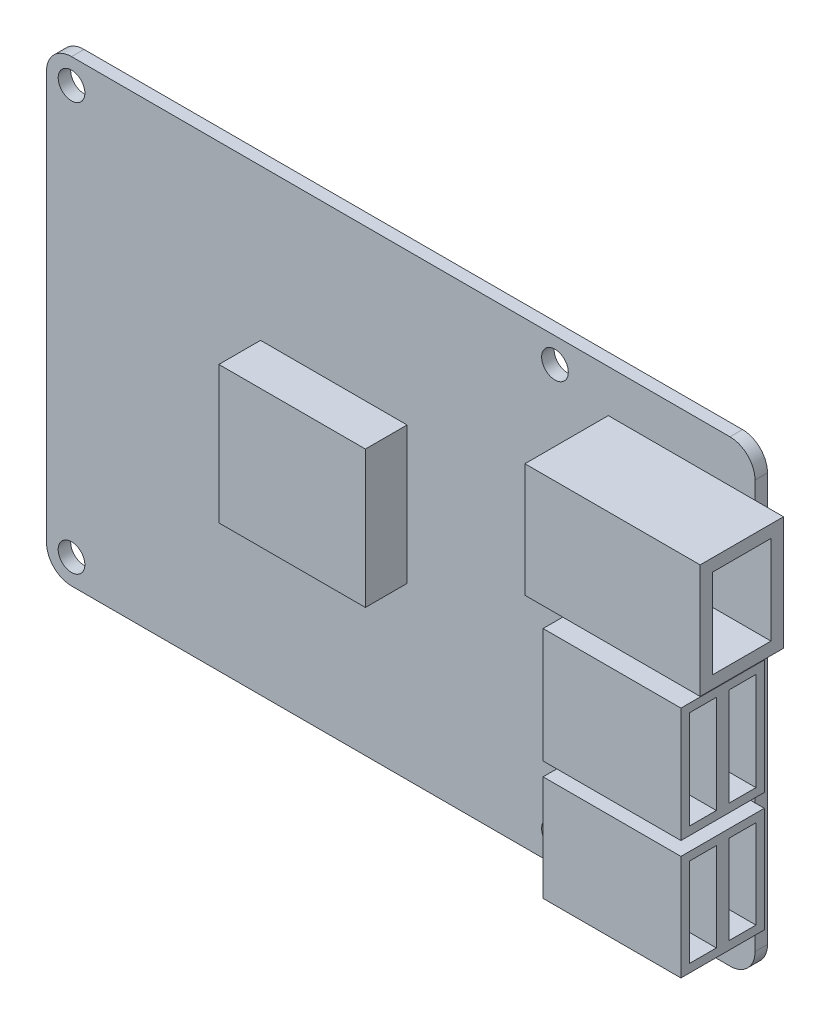
SolidWorks part; units mm, degrees
ref_plane "Front Plane" through (0, 0, 0) normal (0, 0, 1) x (1, 0, 0)
ref_plane "Top Plane" through (0, 0, 0) normal (0, 1, 0) x (1, 0, 0)
ref_plane "Right Plane" through (0, 0, 0) normal (1, 0, 0) x (0, 0, -1)
sketch "Sketch1" plane through (0, 0, 0) normal (0, 0, 1) x (1, 0, 0)
  line L0 (4.3421, -1.9236) -> (89.3421, -1.9236) construction
  line L1 (7.3421, 25.5764) -> (86.3421, 25.5764)
  line L2 (4.3421, 22.5764) -> (4.3421, -26.4236)
  line L3 (7.3421, -29.4236) -> (86.3421, -29.4236)
  line L4 (89.3421, 22.5764) -> (89.3421, -26.4236)
  circle A0 centre (7.3421, 22.5764) radius 1.6
  circle A1 centre (7.3421, -26.4236) radius 1.6
  circle A2 centre (7.3421, 22.5764) radius 1.6
  circle A3 centre (7.3421, -26.4236) radius 1.6
  circle A4 centre (7.3421, 22.5764) radius 1.6
  circle A5 centre (7.3421, -26.4236) radius 1.6
  circle A6 centre (7.3421, 22.5764) radius 1.6
  circle A7 centre (7.3421, -26.4236) radius 1.6
  circle A8 centre (65.3421, -26.4236) radius 1.6
  circle A9 centre (65.3421, 22.5764) radius 1.6
  circle A10 centre (65.3421, -26.4236) radius 1.6
  circle A11 centre (65.3421, 22.5764) radius 1.6
  circle A12 centre (65.3421, -26.4236) radius 1.6
  circle A13 centre (65.3421, 22.5764) radius 1.6
  circle A14 centre (65.3421, -26.4236) radius 1.6
  circle A15 centre (65.3421, 22.5764) radius 1.6
  arc A16 (86.3421, 25.5764) -> (89.3421, 22.5764) centre (86.3421, 22.5764) cw
  arc A17 (86.3421, -29.4236) -> (89.3421, -26.4236) centre (86.3421, -26.4236) ccw
  arc A18 (7.3421, 25.5764) -> (4.3421, 22.5764) centre (7.3421, 22.5764) ccw
  arc A19 (4.3421, -26.4236) -> (7.3421, -29.4236) centre (7.3421, -26.4236) ccw
  point P32 (89.3421, 25.5764)
  point P35 (89.3421, -29.4236)
  point P38 (4.3421, 25.5764)
  dimension "D6" = 3
  dimension "D2" = 55
extrude "Boss-Extrude1" add sketch "Sketch1" along normal blind 1.5 contours L4 L1 L2 L3 A1 A0 A8 A9 | L0 L2 A19 L3 A17 L4 A8 A1 region at (46.9149, 11.7299, 0) region at (46.9149, -15.5772, 0)
sketch "Sketch2" plane through (0, 0, 1.5) normal (0, 0, 1) x (1, 0, 0)
  line L1 (71.7387, 20.4772) -> (92.7595, 20.4772)
  line L2 (71.7387, 20.4772) -> (71.7387, 6.8085)
  line L3 (71.7387, 6.8085) -> (92.7595, 6.8085)
  line L4 (92.7595, 20.4772) -> (92.7595, 6.8085)
  line L5 (73.917, 4.445) -> (90.4556, 4.445)
  line L6 (73.917, 4.445) -> (73.917, -9.32)
  line L7 (73.917, -9.32) -> (90.4556, -9.32)
  line L8 (90.4556, 4.445) -> (90.4556, -9.32)
  line L9 (73.917, -10.9636) -> (90.4556, -10.9636)
  line L10 (73.917, -10.9636) -> (73.917, -23.5987)
  line L11 (73.917, -23.5987) -> (90.4556, -23.5987)
  line L12 (90.4556, -10.9636) -> (90.4556, -23.5987)
extrude "Boss-Extrude2" add sketch "Sketch2" along normal blind 10
sketch "Sketch3" plane through (0, 0, 1.5) normal (0, 0, 1) x (1, 0, 0)
  line L1 (47.6007, 7.435) -> (30.0205, 7.435)
  line L2 (47.6007, 7.435) -> (47.6007, -9.0289)
  line L3 (47.6007, -9.0289) -> (30.0205, -9.0289)
  line L4 (30.0205, 7.435) -> (30.0205, -9.0289)
extrude "Boss-Extrude3" add sketch "Sketch3" along normal blind 5
sketch "Sketch4" plane through (92.7595, 0, 0) normal (1, 0, 0) x (0, 0, -1)
  line L8 (-3, 8.3085) -> (-3, 18.9772)
  line L9 (-3, 18.9772) -> (-10, 18.9772)
  line L10 (-10, 18.9772) -> (-10, 8.3085)
  line L11 (-10, 8.3085) -> (-3, 8.3085)
  line L12 (-3, 8.3085) -> (-3, 18.9772)
  line L13 (-3, 18.9772) -> (-10, 18.9772)
  line L14 (-10, 18.9772) -> (-10, 8.3085)
  line L15 (-10, 8.3085) -> (-3, 8.3085)
  dimension "D1" = 1.5
extrude "Cut-Extrude1" cut sketch "Sketch4" against normal blind 15
sketch "Sketch5" plane through (90.4556, 0, 0) normal (1, 0, 0) x (0, 0, -1)
  line L0 (-6.5, -23.5987) -> (-6.5, 4.445) construction
  line L1 (-11.5, -23.5987) -> (-1.5, -23.5987) construction
  line L2 (-11.5, 4.445) -> (-1.5, 4.445) construction
  line L19 (-2.5, -22.5987) -> (-2.5, -11.9636)
  line L20 (-2.5, -11.9636) -> (-10.5, -11.9636)
  line L21 (-10.5, -11.9636) -> (-10.5, -22.5987)
  line L22 (-10.5, -22.5987) -> (-2.5, -22.5987)
  line L23 (-2.5, -22.5987) -> (-2.5, -11.9636)
  line L24 (-2.5, -11.9636) -> (-5.75, -11.9636)
  line L25 (-10.5, -11.9636) -> (-10.5, -22.5987)
  line L26 (-10.5, -22.5987) -> (-7.25, -22.5987)
  line L27 (-5.75, -22.5987) -> (-5.75, -11.9636)
  line L28 (-7.25, -22.5987) -> (-7.25, -11.9636)
  line L29 (-5.75, -23.5987) -> (-5.75, 4.445) construction
  line L30 (-5.75, -22.5987) -> (-2.5, -22.5987)
  line L31 (-2.5, -8.32) -> (-2.5, 3.445)
  line L32 (-2.5, 3.445) -> (-10.5, 3.445)
  line L33 (-10.5, 3.445) -> (-10.5, -8.32)
  line L34 (-10.5, -8.32) -> (-2.5, -8.32)
  line L35 (-2.5, -8.32) -> (-2.5, 3.445)
  line L36 (-2.5, 3.445) -> (-5.75, 3.445)
  line L37 (-10.5, 3.445) -> (-10.5, -8.32)
  line L38 (-10.5, -8.32) -> (-7.25, -8.32)
  line L39 (-7.25, -23.5987) -> (-7.25, 4.445) construction
  line L40 (-7.25, -11.9636) -> (-10.5, -11.9636)
  line L41 (-7.25, -8.32) -> (-7.25, 3.445)
  line L42 (-5.75, -8.32) -> (-5.75, 3.445)
  line L43 (-5.75, -8.32) -> (-2.5, -8.32)
  line L44 (-7.25, 3.445) -> (-10.5, 3.445)
  dimension "D1" = 1
  dimension "D2" = 1
  dimension "D3" = 0.75
  dimension "D4" = 0.75
extrude "Cut-Extrude2" cut sketch "Sketch5" against normal blind 15
